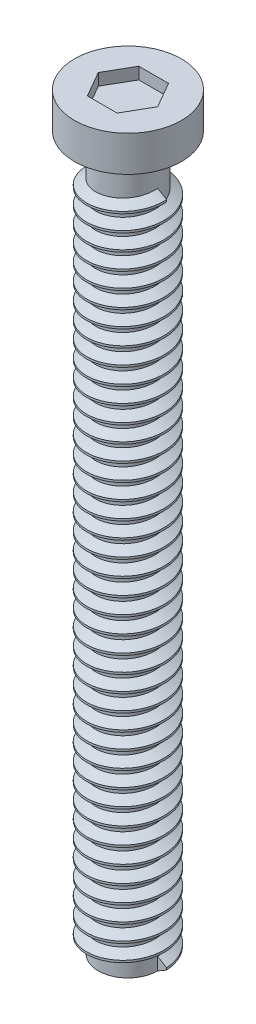
SolidWorks part; units mm, degrees
ref_plane "Front Plane" through (0, 0, 0) normal (0, 0, 1) x (1, 0, 0)
ref_plane "Top Plane" through (0, 0, 0) normal (0, 1, 0) x (1, 0, 0)
ref_plane "Right Plane" through (0, 0, 0) normal (1, 0, 0) x (0, 0, -1)
sketch "Sketch1" plane through (0, 0, 0) normal (0, 1, 0) x (1, 0, 0)
  circle A0 centre (0, 0) radius 1.25
  dimension "D1" = 2.5
extrude "Boss-Extrude1" add sketch "Sketch1" along normal blind 30
sketch "Sketch4" plane through (0, 30, 0) normal (0, 1, 0) x (1, 0, 0)
  circle A0 centre (0, 0) radius 2.25
  dimension "D1" = 4.5
extrude "Boss-Extrude2" add sketch "Sketch4" along normal blind 1.5
sketch "Sketch5" plane through (0, 31.5, 0) normal (0, 1, 0) x (1, 0, 0)
  line L1 (1.25, 0) -> (0.625, 1.0825)
  line L2 (0.625, 1.0825) -> (-0.625, 1.0825)
  line L3 (-0.625, 1.0825) -> (-1.25, 0)
  line L4 (-1.25, 0) -> (-0.625, -1.0825)
  line L5 (-0.625, -1.0825) -> (0.625, -1.0825)
  line L6 (0.625, -1.0825) -> (1.25, 0)
  circle A0 centre (0, 0) radius 1.0825 construction
  dimension "D1" = 1.25
extrude "Cut-Extrude1" cut sketch "Sketch5" against normal blind 0.5
thread "Thread1" pitch 0.7 method extrude profile "Thread Profile1" start angle 0, offset 0, length 28, pitch 0.7, diameter 2.5
ref_plane "Plane1" through (1.25, 0, 0) normal (0, 0, 1) x (1, 0, 0)
sketch "Thread Profile1" plane through (1.25, 0, 0) normal (0, 0, 1) x (1, 0, 0)
  line L0 (0, 0) -> (0, 0.7) construction
  line L1 (0, 0) -> (0.3789, 0.2187)
  line L2 (0.3789, 0.2187) -> (0.3789, 0.3062)
  line L3 (0.3789, 0.3062) -> (0, 0.525)
  line L4 (0.3789, 0.2625) -> (0, 0.2625) construction
  line L11 (0, 0) -> (0, 0.525)
  point P2 (0, 0)
  dimension "Pitch" = 0.7
  dimension "Profile_Angle" = 60
  dimension "Profile_Land" = 0.0875
  dimension "Profile_Height" = 0.3789
